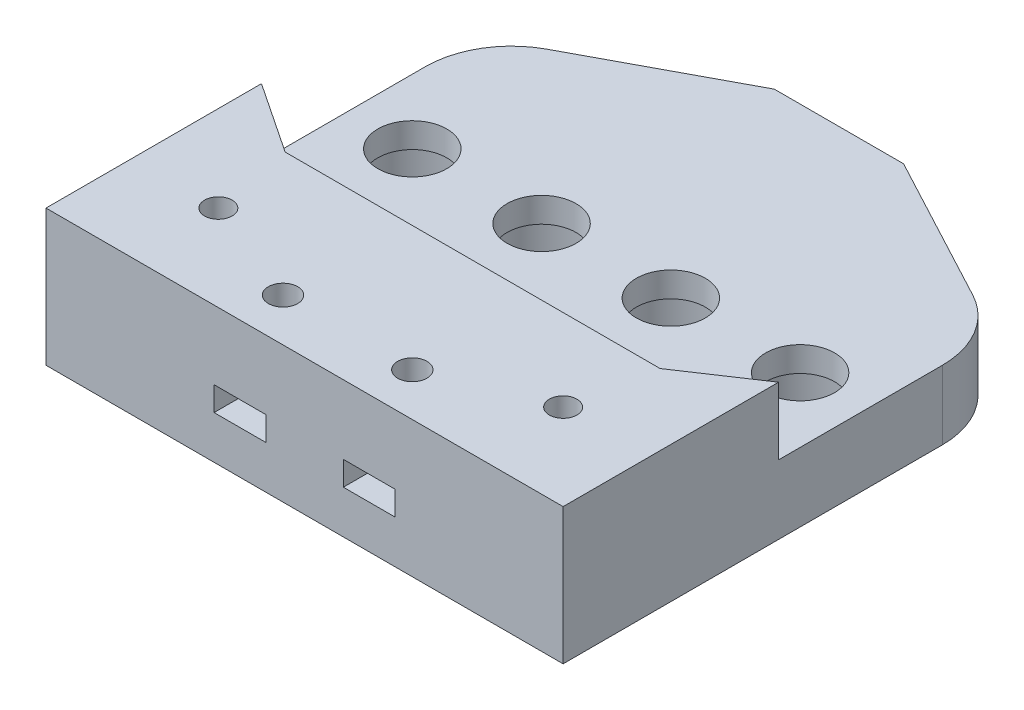
SolidWorks part; units mm, degrees
ref_plane "Front Plane" through (0, 0, 0) normal (0, 0, 1) x (1, 0, 0)
ref_plane "Top Plane" through (0, 0, 0) normal (0, 1, 0) x (1, 0, 0)
ref_plane "Right Plane" through (0, 0, 0) normal (1, 0, 0) x (0, 0, -1)
sketch "Sketch2" plane through (0, 0, 0) normal (0, 1, 0) x (1, 0, 0)
  line L0 (0, 0) -> (0, 35)
  line L1 (0, 35) -> (22.5, 47)
  line L2 (22.5, 47) -> (37.5, 47)
  line L3 (37.5, 47) -> (60, 35)
  line L4 (60, 35) -> (60, 0)
  line L5 (60, 0) -> (0, 0)
  line L6 (22.5, 20) -> (37.5, 20) construction
  line L7 (30, 47) -> (30, 0) construction
  circle A0 centre (7.5, 20) radius 4
  circle A1 centre (22.5, 20) radius 4
  circle A2 centre (37.5, 20) radius 4
  circle A3 centre (52.5, 20) radius 4
  point P17 (30, 20)
  dimension "D5" = 8
  dimension "D7" = 15
  dimension "D8" = 15
  dimension "D9" = 15
  dimension "D6" = 20
  dimension "D1" = 60
  dimension "D2" = 35
  dimension "D3" = 15
  dimension "D4" = 12
extrude "Boss-Extrude1" add sketch "Sketch2" along normal blind 8
sketch "Sketch3" plane through (0, 8, 0) normal (0, 1, 0) x (1, 0, 0)
  line L0 (0, 0) -> (0, 10)
  line L1 (0, 35) -> (0, 0) construction
  line L2 (0, 10) -> (15, 0)
  line L3 (0, 0) -> (60, 0) construction
  line L4 (15, 0) -> (0, 0)
  line L5 (60, 0) -> (60, 10)
  line L6 (60, 0) -> (60, 35) construction
  line L7 (60, 10) -> (45, 0)
  line L8 (45, 0) -> (60, 0)
  line L9 (51.75, 4.5) -> (8.25, 4.5)
  line M8 (0, 0) -> (60, 0)
  line M9 (60, 0) -> (60, 35)
  line M13 (0, 35) -> (0, 0)
  dimension "D1" = 15
  dimension "D2" = 10
  dimension "D3" = 4.5
extrude "Boss-Extrude2" add sketch "Sketch3" along normal blind 7.8 contours L2 M13 M8 | L7 L9 L2 M8 | L7 M9 M8 region at (5, 8, -3.3333) region at (30, 8, -2.3878) region at (55, 8, -3.3333)
sketch "Sketch4" plane through (0, 15.8, 0) normal (0, 1, 0) x (1, 0, 0)
  line L0 (0, 0) -> (60, 0) construction
  line L1 (0, 10) -> (0, 0) construction
  line L2 (60, 0) -> (60, 10) construction
  circle A0 centre (3, 4.25) radius 1.7
  circle A1 centre (57, 4.25) radius 1.7
  dimension "D1" = 3.4
  dimension "D2" = 4.25
  dimension "D3" = 3
  dimension "D4" = 3
extrude "Cut-Extrude1" [suppressed] cut sketch "Sketch4" against normal through all
sketch "Sketch5" plane through (0, 0, 0) normal (0, 1, 0) x (1, 0, 0)
  circle A0 centre (7.5, 20) radius 6.55
  circle A1 centre (22.5, 20) radius 6.55
  circle A2 centre (37.5, 20) radius 6.55
  circle A3 centre (52.5, 20) radius 6.55
  dimension "D1" = 13.1
extrude "Cut-Extrude2" cut sketch "Sketch5" along normal blind 5.1
fillet "Fillet1" radius 10 2 edges at (0, 4, -35) (60, 4, -35)
sketch "Sketch6" plane through (0, 0, 0) normal (0, -1, 0) x (-1, 0, 0)
  line L0 (-25, 42.25) -> (-35, 42.25) construction
  line L1 (-37.5, 47) -> (-22.5, 47) construction
  circle A0 centre (-25, 42.25) radius 2.6
  circle A1 centre (-35, 42.25) radius 2.6
  circle A2 centre (-35, 4.25) radius 2.6
  circle A3 centre (-25, 4.25) radius 2.6
  point P10 (-30, 47)
  point P11 (-30, 42.25)
  dimension "D1" = 5.2
  dimension "D2" = 10
  dimension "D3" = 38
  dimension "D4" = 4.75
extrude "Cut-Extrude3" cut sketch "Sketch6" against normal blind 6
sketch "Sketch7" plane through (0, 0, 0) normal (0, 0, 1) x (1, 0, 0)
  line L1 (0, 15.8) -> (60, 15.8)
  line L2 (0, 15.8) -> (0, 0)
  line L3 (0, 0) -> (60, 0)
  line L4 (60, 15.8) -> (60, 0)
extrude "Boss-Extrude3" add sketch "Sketch7" along normal blind 15
sketch "Sketch8" plane through (0, 0, 0) normal (0, -1, 0) x (-1, 0, 0)
  line L0 (0, 29) -> (0, -15) construction
  line L1 (-60, -15) -> (-60, 29) construction
  line L2 (0, -15) -> (-60, -15) construction
  circle A0 centre (-10, -5) radius 1.6
  circle A1 centre (-50, -5) radius 1.6
  point P8 (0, 0)
  point P9 (-50, -9.2436)
  dimension "D1" = 3.2
  dimension "D2" = 10
  dimension "D3" = 10
  dimension "D4" = 10
extrude "Cut-Extrude4" cut sketch "Sketch8" against normal up to next
sketch "Sketch9" plane through (0, 0, 0) normal (0, -1, 0) x (-1, 0, 0)
  line L1 (-51.7321, -2) -> (-53.4641, -5)
  line L2 (-53.4641, -5) -> (-51.7321, -8)
  line L3 (-51.7321, -8) -> (-48.2679, -8)
  line L4 (-48.2679, -8) -> (-46.5359, -5)
  line L5 (-46.5359, -5) -> (-48.2679, -2)
  line L6 (-48.2679, -2) -> (-51.7321, -2)
  line L7 (-13.4641, -5) -> (-11.7321, -8)
  line L8 (-11.7321, -8) -> (-8.2679, -8)
  line L9 (-8.2679, -8) -> (-6.5359, -5)
  line L10 (-6.5359, -5) -> (-8.2679, -2)
  line L11 (-8.2679, -2) -> (-11.7321, -2)
  line L12 (-11.7321, -2) -> (-13.4641, -5)
  circle A0 centre (-50, -5) radius 3 construction
  circle A1 centre (-10, -5) radius 3 construction
  dimension "D1" = 6
extrude "Cut-Extrude5" cut sketch "Sketch9" against normal blind 5
sketch "Sketch10" plane through (0, 0, 0) normal (0, -1, 0) x (-1, 0, 0)
  line L0 (-22.5, -10) -> (-37.5, -10) construction
  line L1 (0, -15) -> (-60, -15) construction
  circle A0 centre (-22.5, -10) radius 1.7
  circle A1 centre (-37.5, -10) radius 1.7
  point P6 (-30, -15)
  point P7 (-30, -10)
  dimension "D1" = 3.4
  dimension "D2" = 15
  dimension "D3" = 5
extrude "Cut-Extrude6" cut sketch "Sketch10" against normal through all
sketch "Sketch11" plane through (0, 0, 0) normal (0, -1, 0) x (-1, 0, 0)
  line L0 (-25.5, -11.7321) -> (-25.5, -15)
  line L1 (-25.5, -11.7321) -> (-22.5, -13.4641)
  line L2 (-22.5, -13.4641) -> (-19.5, -11.7321)
  line L3 (-19.5, -11.7321) -> (-19.5, -8.2679)
  line L4 (-19.5, -8.2679) -> (-22.5, -6.5359)
  line L5 (-22.5, -6.5359) -> (-25.5, -8.2679)
  line L6 (-25.5, -8.2679) -> (-25.5, -11.7321)
  line L7 (-40.5, -11.7321) -> (-37.5, -13.4641)
  line L8 (-37.5, -13.4641) -> (-34.5, -11.7321)
  line L9 (-34.5, -11.7321) -> (-34.5, -8.2679)
  line L10 (-34.5, -8.2679) -> (-37.5, -6.5359)
  line L11 (-37.5, -6.5359) -> (-40.5, -8.2679)
  line L12 (-40.5, -8.2679) -> (-40.5, -11.7321)
  line L13 (0, -15) -> (-60, -15) construction
  line L14 (-25.5, -15) -> (-19.5, -15)
  line L15 (-19.5, -15) -> (-19.5, -11.7321)
  line L16 (-34.5, -11.7321) -> (-34.5, -15)
  line L17 (-34.5, -15) -> (-40.5, -15)
  line L18 (-40.5, -15) -> (-40.5, -11.7321)
  circle A0 centre (-22.5, -10) radius 3 construction
  circle A1 centre (-37.5, -10) radius 3 construction
  circle M13 centre (-22.5, -10) radius 1.7
  circle M14 centre (-37.5, -10) radius 1.7
  line M42 (-60, -15) -> (0, -15)
  dimension "D1" = 6
extrude "Cut-Extrude7" cut sketch "Sketch11" against normal blind 2.8 from offset 5 contours L5 L6 L1 L2 L3 L4 M13 | L15 L2 L1 L0 M42 | L11 L12 L7 L8 L9 L10 M14 | L18 L16 L8 L7 M42 region at (22.5, 0, 13.747) region at (25.4083, 0, 10) region at (37.5, 0, 13.747) region at (36.0458, 0, 12.5187) offset against normal yes
